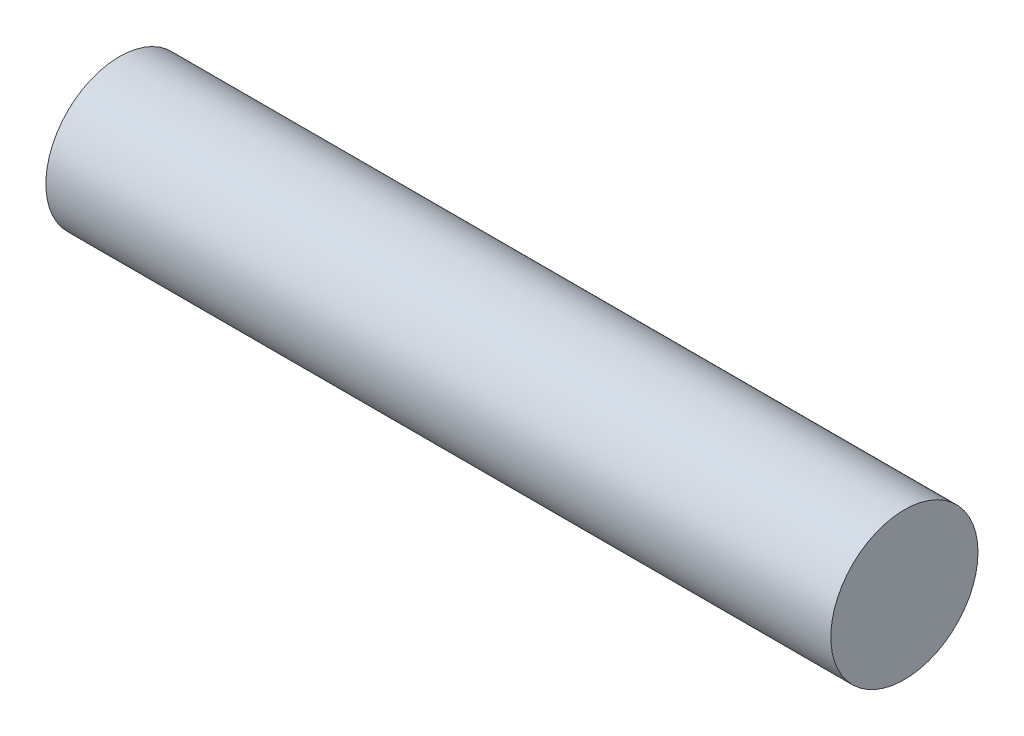
SolidWorks part; units mm, degrees
ref_plane "Front Plane" through (0, 0, 0) normal (0, 0, 1) x (1, 0, 0)
ref_plane "Top Plane" through (0, 0, 0) normal (0, 1, 0) x (1, 0, 0)
ref_plane "Right Plane" through (0, 0, 0) normal (1, 0, 0) x (0, 0, -1)
sketch "Sketch1" plane through (0, 0, 0) normal (1, 0, 0) x (0, 0, -1)
  circle A0 centre (0, 0) radius 9.525
  dimension "D1" = 19.05
extrude "Boss-Extrude1" add sketch "Sketch1" along normal blind 101.6
